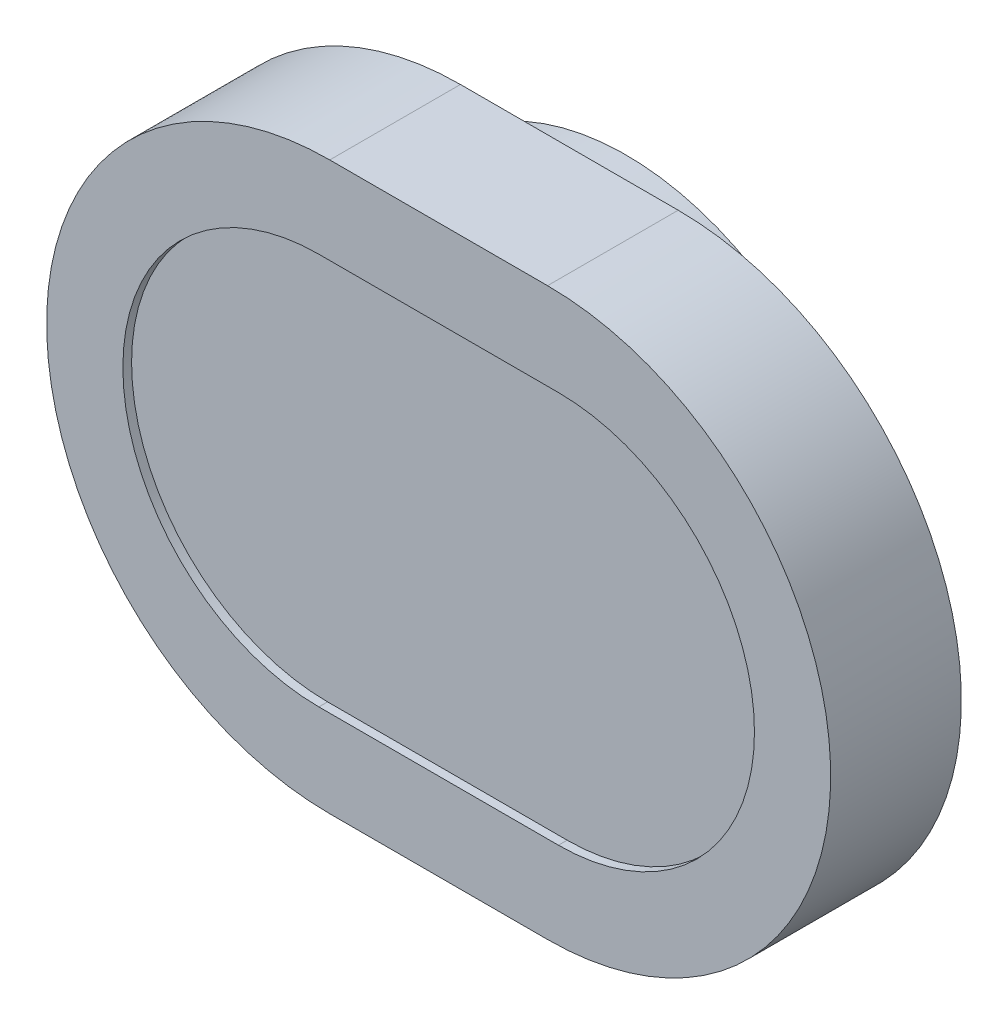
SolidWorks part; units mm, degrees
material "ABS"
ref_plane "Спереди" through (0, 0, 0) normal (0, 0, 1) x (1, 0, 0)
ref_plane "Сверху" through (0, 0, 0) normal (0, 1, 0) x (1, 0, 0)
ref_plane "Справа" through (0, 0, 0) normal (1, 0, 0) x (0, 0, -1)
ref_axis "Ось1" through (0, 0, 50) along (0, 0, -1)
sketch "Эскиз1" plane through (0, 0, 0) normal (0, 0, 1) x (1, 0, 0)
  circle A0 centre (0, 0) radius 5.7
  dimension "D1" = 11.4
extrude "Бобышка-Вытянуть1" add sketch "Эскиз1" along normal blind 1.3
sketch "Эскиз2" plane through (0, 0, 1.3) normal (0, 0, 1) x (1, 0, 0)
  line L0 (-2.5, 0) -> (2.5, 0) construction
  line L1 (-2.5, 6.5) -> (2.5, 6.5)
  line L2 (-2.5, -6.5) -> (2.5, -6.5)
  arc A0 (-2.5, 6.5) -> (-2.5, -6.5) centre (-2.5, 0) ccw
  arc A1 (2.5, -6.5) -> (2.5, 6.5) centre (2.5, 0) ccw
  point P2 (0, 0)
  point P8 (-9, 0)
  point P9 (9, 0)
  dimension "D1" = 18
  dimension "D2" = 13
extrude "Бобышка-Вытянуть2" add sketch "Эскиз2" along normal blind 2.8
sketch "Эскиз3" plane through (0, 0, 4.1) normal (0, 0, 1) x (1, 0, 0)
  line L0 (-2.75, 0) -> (2.75, 0) construction
  line L1 (-2.75, 4.5) -> (2.75, 4.5)
  line L2 (-2.75, -4.5) -> (2.75, -4.5)
  line L3 (-2.5, 0) -> (2.5, 0) construction
  line L4 (-2.5, 6.5) -> (2.5, 6.5)
  line L5 (-2.5, -6.5) -> (2.5, -6.5)
  line L6 (2.5, 6.5) -> (-2.5, 6.5) construction
  arc A0 (-2.75, 4.5) -> (-2.75, -4.5) centre (-2.75, 0) ccw
  arc A1 (2.75, -4.5) -> (2.75, 4.5) centre (2.75, 0) ccw
  arc A2 (-2.5, 6.5) -> (-2.5, -6.5) centre (-2.5, 0) ccw
  arc A3 (2.5, -6.5) -> (2.5, 6.5) centre (2.5, 0) ccw
  arc A4 (-2.5, 6.5) -> (-2.5, -6.5) centre (-2.5, 0) ccw construction
  point P2 (0, 0)
  point P8 (7.25, 0)
  point P9 (-7.25, 0)
  point P12 (0, 0)
  point P19 (0, 6.5)
  point P20 (0, 6.5)
  point P24 (-9, 0)
  point P25 (-9, 0)
  dimension "D1" = 9
  dimension "D2" = 14.5
extrude "Бобышка-Вытянуть3" add sketch "Эскиз3" along normal blind 0.2
